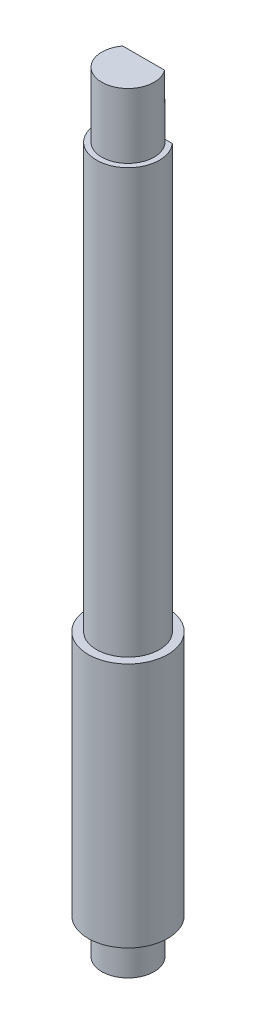
SolidWorks part; units mm, degrees
ref_plane "前视基准面" through (0, 0, 0) normal (0, 0, 1) x (1, 0, 0)
ref_plane "上视基准面" through (0, 0, 0) normal (0, 1, 0) x (1, 0, 0)
ref_plane "右视基准面" through (0, 0, 0) normal (1, 0, 0) x (0, 0, -1)
sketch "草图1" plane through (0, 0, 0) normal (0, 0, 1) x (1, 0, 0)
  line L0 (0, 5.9545) -> (0, -34.75)
  line L1 (1.5, 2.8545) -> (1.5, -17.3955)
  line L2 (1.5, -17.3955) -> (1.9, -17.3955)
  line L3 (1.9, -17.3955) -> (1.9, -29.1455)
  line L4 (1.25, 5.9545) -> (1.25, 2.8545)
  line L6 (1.25, -30.8455) -> (0, -30.8455)
  line L7 (1.5, 2.8545) -> (1.25, 2.8545)
  line L9 (1.25, 5.9545) -> (0, 5.9545)
  line L10 (1.9, -29.1455) -> (1.25, -29.1455)
  line L11 (1.25, -29.1455) -> (1.25, -30.8455)
  dimension "D1" = 23.35
  dimension "D2" = 3
  dimension "D3" = 1.25
  dimension "D4" = 1.9
  dimension "D5" = 36.8
  dimension "D6" = 1.7
  dimension "D7" = 3.1
  dimension "D8" = 1.25
revolve "旋转2" add sketch "草图1" angle 360 about L0 region at (0.8133, -13.4077, 0)
sketch "草图4" plane through (0, 5.9545, 0) normal (0, 1, 0) x (1, 0, 0)
  line L0 (-1.118, 1) -> (1.118, 1)
  arc A1 (1.118, 1) -> (-1.118, 1) centre (0, 0) ccw
  dimension "D2" = 3
  dimension "D1" = 1
extrude "切除-拉伸2" cut sketch "草图4" against normal up to surface (23.35 mm away) up to face at (-1.9, -17.3955, 0)
sketch "草图5" plane through (0, 5.9545, 0) normal (0, 1, 0) x (1, 0, 0)
  line L0 (-1, 0.75) -> (1, 0.75)
  line L2 (0.75, 1) -> (-0.75, 1)
  arc A1 (-0.75, 1) -> (0.75, 1) centre (0, 0) ccw
  arc A2 (1, 0.75) -> (-1, 0.75) centre (0, 0) ccw
  dimension "D2" = 0.75
  dimension "D1" = 0
extrude "切除-拉伸3" cut sketch "草图5" against normal blind 1.4
sketch "草图7" plane through (0, 5.9545, 0) normal (0, 1, 0) x (1, 0, 0)
  line L0 (0, 0) -> (3.7049, -2.864)
ref_plane "基准面1" through (0, 5.9545, 0) normal (0.7912, 0, 0.6116) x (0.6116, 0, -0.7912)
sketch "草图8" plane through (0, 5.9545, 0) normal (0.7912, 0, 0.6116) x (0.6116, 0, -0.7912)
  line L0 (-0.7, -18.9) -> (-0.7, -21.9)
  line L1 (0.7, -18.9) -> (0.7, -21.9)
  line L2 (-0.7, -21.9) -> (0.7, -21.9)
  line L3 (1.475, -23.35) -> (-1.5, -23.35) construction
  arc A0 (-0.7, -18.9) -> (0.7, -18.9) centre (0, -18.9) cw
  dimension "D1" = 1.4
  dimension "D2" = 1.45
  dimension "D3" = 3
ref_plane "基准面2" through (0, -13.1455, 0) normal (0, 1, 0) x (1, 0, 0)
ref_axis "基准轴1" through (0, -7.6527, 0) along (0, 1, 0)
ref_point "点1"
